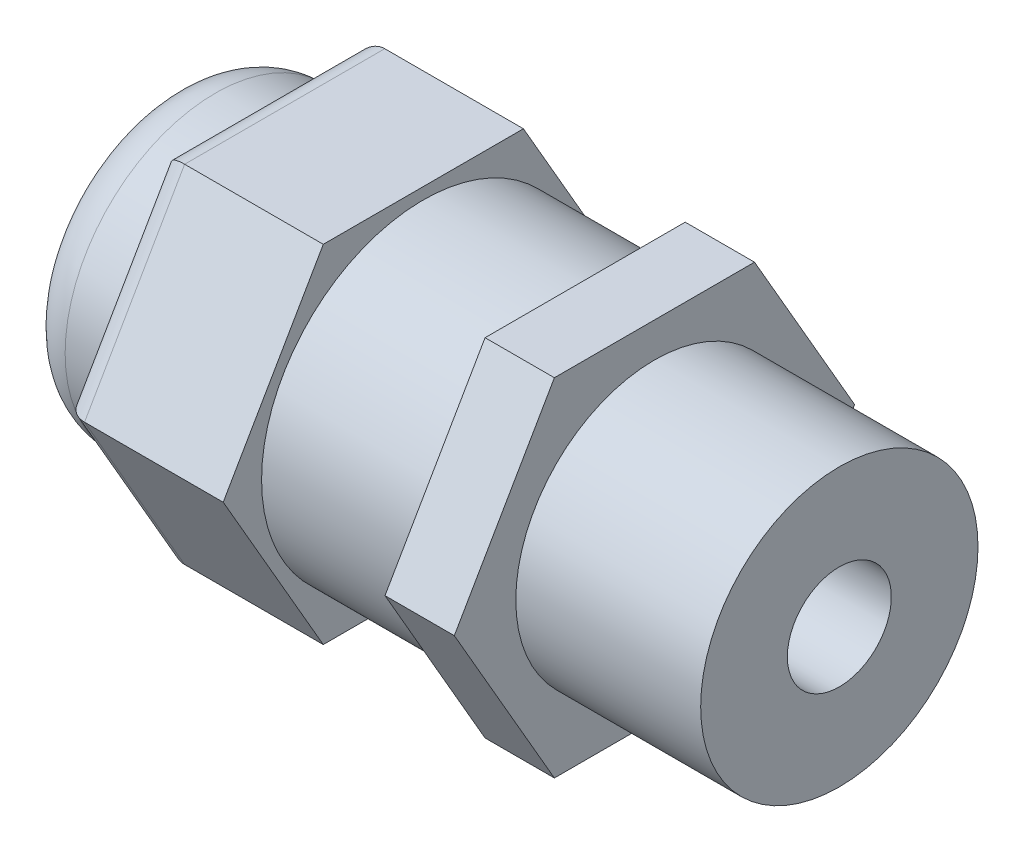
SolidWorks part; units mm, degrees
material "Nylon 6/10"
ref_plane "Plan de face" through (0, 0, 0) normal (0, 0, 1) x (1, 0, 0)
ref_plane "Plan de dessus" through (0, 0, 0) normal (0, 1, 0) x (1, 0, 0)
ref_plane "Plan de droite" through (0, 0, 0) normal (1, 0, 0) x (0, 0, -1)
sketch "Sketch1" plane through (0, 0, 0) normal (0, 0, 1) x (1, 0, 0)
  line L0 (-13.3953, 0) -> (28.186, 0) construction
  line L1 (11, 0) -> (11, 6)
  line L2 (11, 6) -> (0, 6)
  line L3 (0, 6) -> (0, 7)
  line L4 (0, 7) -> (-7, 7)
  line L5 (-7, 7) -> (-7, 0)
  line L6 (-7, 0) -> (11, 0)
  dimension "D1" = 12
  dimension "D2" = 11
  dimension "D3" = 14
  dimension "D4" = 7
revolve "Revolve1" add sketch "Sketch1" angle 360 about L0
sketch "Sketch2" plane through (0, 0, 0) normal (1, 0, 0) x (0, 0, -1)
  line L1 (4.3301, -7.5) -> (8.6603, 0)
  line L2 (8.6603, 0) -> (4.3301, 7.5)
  line L3 (4.3301, 7.5) -> (-4.3301, 7.5)
  line L4 (-4.3301, 7.5) -> (-8.6603, 0)
  line L5 (-8.6603, 0) -> (-4.3301, -7.5)
  line L6 (-4.3301, -7.5) -> (4.3301, -7.5)
  circle A0 centre (0, 0) radius 7.5 construction
  dimension "D1" = 15
extrude "Boss-Extrude1" add sketch "Sketch2" along normal blind 3
sketch "Sketch3" plane through (-7, 0, 0) normal (-1, 0, 0) x (0, 0, 1)
  line L1 (4.3301, -7.5) -> (8.6603, 0)
  line L2 (8.6603, 0) -> (4.3301, 7.5)
  line L3 (4.3301, 7.5) -> (-4.3301, 7.5)
  line L4 (-4.3301, 7.5) -> (-8.6603, 0)
  line L5 (-8.6603, 0) -> (-4.3301, -7.5)
  line L6 (-4.3301, -7.5) -> (4.3301, -7.5)
  circle A0 centre (0, 0) radius 7.5 construction
  dimension "D1" = 15
extrude "Boss-Extrude2" add sketch "Sketch3" along normal blind 7
sketch "Sketch4" plane through (-14, 0, 0) normal (-1, 0, 0) x (0, 0, 1)
  circle A0 centre (0, 0) radius 6.5
  dimension "D1" = 13
extrude "Boss-Extrude3" add sketch "Sketch4" along normal blind 4
fillet "Fillet1" radius 2 1 edges at (-18, 0, 6.5)
fillet "Fillet2" radius 1 6 edges at (-14, 3.75, -6.4952) (-14, -3.75, -6.4952) (-14, -7.5, 0) (-14, -3.75, 6.4952) (-14, 7.5, 0) (-14, 3.75, 6.4952)
sketch "Sketch5" plane through (-18, 0, 0) normal (-1, 0, 0) x (0, 0, 1)
  circle A0 centre (0, 0) radius 2.25
  dimension "D1" = 4.5
extrude "Cut-Extrude1" cut sketch "Sketch5" against normal through all
